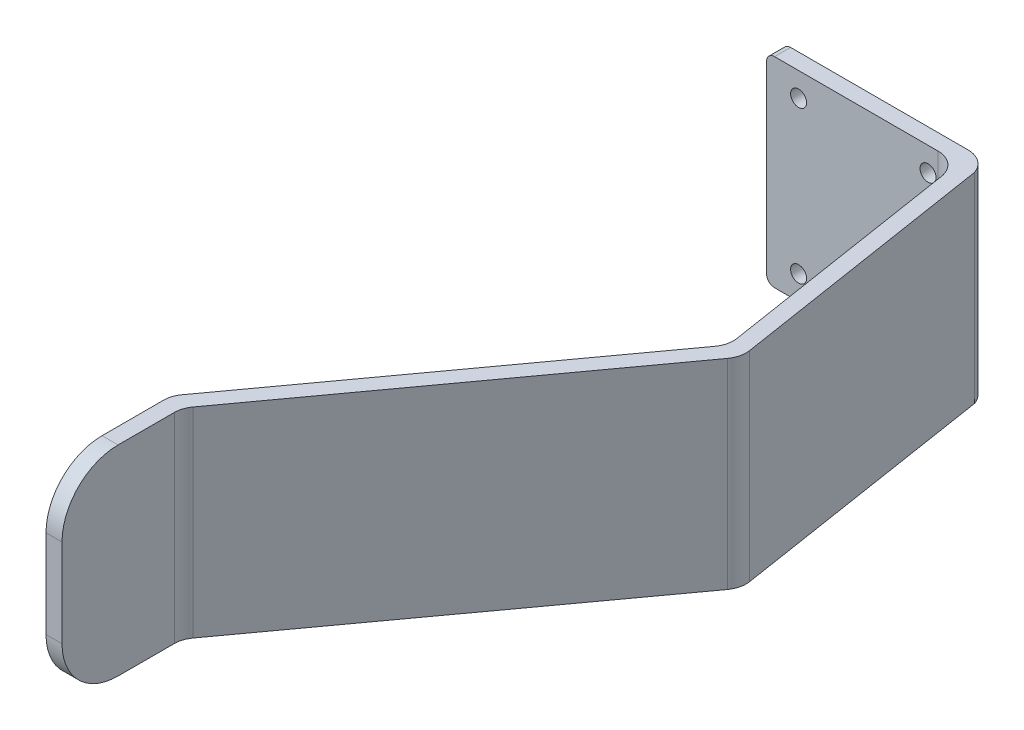
SolidWorks part; units mm, degrees
material "1060 Alloy"
ref_plane "Front Plane" through (0, 0, 0) normal (0, 0, 1) x (1, 0, 0)
ref_plane "Top Plane" through (0, 0, 0) normal (0, 1, 0) x (1, 0, 0)
ref_plane "Right Plane" through (0, 0, 0) normal (1, 0, 0) x (0, 0, -1)
sketch "Sketch1" plane through (0, 0, 0) normal (0, 1, 0) x (1, 0, 0)
  line L0 (-13, -75.3491) -> (-13, -76)
  line L1 (-13, 1) -> (13, 1)
  line L2 (-13, 1) -> (-13, -1)
  line L3 (-13, -1) -> (13, -1)
  line L4 (13, 1) -> (13, -1)
  line L5 (-13, 1) -> (13, -1) construction
  line L6 (-13, -1) -> (13, 1) construction
  line L7 (13, -1) -> (18.4271, -35.5767)
  line L8 (-13, -76) -> (-11, -76)
  line L9 (-13, -76) -> (-13, -91)
  line L10 (-13, -91) -> (-11, -91)
  line L11 (-11, -76) -> (-11, -91)
  line L12 (-11, -76) -> (18.4271, -35.5767)
  line L13 (11.0242, -1.3101) -> (16.3229, -35.0689)
  line L14 (-12.6169, -74.8229) -> (16.3229, -35.0689)
  line L15 (11.0242, -1.3101) -> (10.9755, -1)
  line L16 (-12.6169, -74.8229) -> (16.8102, -34.3996) construction
  line L17 (11.0242, -1.3101) -> (16.4513, -35.8868) construction
  line L18 (-12.6169, -74.8229) -> (-13, -75.3491)
  point P0 (0, 0)
  dimension "D1" = 26
  dimension "D2" = 2
  dimension "D4" = 15
  dimension "D5" = 2
  dimension "D6" = 35
  dimension "D7" = 50
  dimension "D8" = 2
  dimension "D9" = 2
extrude "Boss-Extrude1" add sketch "Sketch1" along normal blind 25 contours L14 L18 L0 L8 L12 L7 L3 L15 L13 | L11 L8 L9 L10 | L4 L1 L2 L3 region at (-12.151, 0, 75.5646) region at (-12, 0, 83.5) region at (0, 0, 0)
sketch "Sketch2" plane through (10.5584, 0, -1.6572) normal (-0.9879, 0, 0.1551) x (0.1551, 0, 0.9879)
  line L0 (19.9328, 12.5) -> (19.9328, 25)
  line L3 (37.1758, 25) -> (2.6898, 25) construction
  line L4 (2.6898, 25) -> (2.6898, 0) construction
  line L6 (2.6898, 12.5) -> (19.9328, 12.5)
  line L7 (19.9328, 12.5) -> (37.1758, 12.5)
  line L8 (37.1758, 25) -> (37.1758, 0) construction
  line L9 (19.9328, 12.5) -> (19.9328, 0)
  line L10 (37.1758, 0) -> (2.6898, 0) construction
  line L11 (11.3113, 12.5) -> (11.3113, 18.75)
  line L12 (11.3113, 18.75) -> (19.9328, 18.75)
  circle A0 centre (11.3113, 18.75) radius 2.5
  circle A1 centre (28.5543, 18.75) radius 2.5
  circle A2 centre (11.3113, 6.25) radius 2.5
  circle A3 centre (28.5543, 6.25) radius 2.5
  dimension "D1" = 5
extrude "Boss-Extrude2" add sketch "Sketch2" along normal blind 2 contours A1 | L11 A0 L12 | L12 A0 L11 | A2 | A3 region at (12.4769, 17.689, 10.5654) region at (12.2575, 19.1037, 9.1678) region at (14.9861, 18.75, 26.5517) region at (12.3124, 6.25, 9.5172) region at (14.9861, 6.25, 26.5517)
sketch "Sketch3" plane through (27.3553, 0, 19.914) normal (-0.8085, 0, -0.5885) x (-0.5885, 0, 0.8085)
  line L0 (18.7453, 12.5) -> (43.6568, 12.5)
  line L3 (43.6568, 0) -> (43.6568, 12.5)
  line L4 (68.5683, 0) -> (18.7453, 0) construction
  line L5 (18.7453, 25) -> (18.7453, 0) construction
  line L6 (43.6568, 12.5) -> (43.6568, 25)
  line L7 (68.5683, 25) -> (18.7453, 25) construction
  line L8 (31.2011, 12.5) -> (31.2011, 18.75)
  line L9 (31.2011, 18.75) -> (43.6568, 18.75)
  circle A0 centre (31.2011, 18.75) radius 2.5
  circle A1 centre (56.1125, 18.75) radius 2.5
  circle A2 centre (31.2011, 6.25) radius 2.5
  circle A3 centre (56.1125, 6.25) radius 2.5
  dimension "D1" = 5
extrude "Boss-Extrude3" add sketch "Sketch3" along normal blind 2 contours L8 A0 L9 | L9 A0 L8 | A2 | A3 | A1 region at (9.2003, 19.1037, 44.853) region at (8.3677, 17.689, 45.9968) region at (-5.6693, 18.75, 65.2791) region at (8.9922, 6.25, 45.139) region at (-5.6693, 6.25, 65.2791)
fillet "Fillet1" radius 2.5 8 edges at (-8.7576, 18.75, 66.1232) (-8.7576, 6.25, 66.1232) (5.9039, 6.25, 45.983) (5.9039, 18.75, 45.983) (13.3979, 18.75, 29.3316) (13.3979, 6.25, 29.3316) (10.7242, 6.25, 12.2971) (10.7242, 18.75, 12.2971)
fillet "Fillet2" radius 7 2 edges at (-12, 0, 91) (-12, 25, 91)
fillet "Fillet3" radius 1 2 edges at (-13, 0, 0) (-13, 25, 0)
fillet "Fillet4" radius 3 2 edges at (13, 12.5, -1) (10.9755, 12.5, 1)
fillet "Fillet5" radius 3 2 edges at (18.4271, 12.5, 35.5767) (16.3229, 12.5, 35.0689)
fillet "Fillet6" radius 3 2 edges at (-11, 12.5, 76) (-13, 12.5, 75.3491)
sketch "Sketch8" plane through (0, 0, -1) normal (0, 0, -1) x (-1, 0, 0)
  line L0 (-10.1716, 22) -> (-7.1716, 22)
  line L1 (-10.1716, 25) -> (-10.1716, 0) construction
  line L2 (-7.1716, 22) -> (-7.1716, 25)
  line L3 (12, 25) -> (-10.1716, 25) construction
  line L4 (-10.1716, 12.5) -> (13, 12.5)
  line L5 (13, 24) -> (13, 1) construction
  line L6 (0.9142, 25) -> (0.9142, 0)
  line L7 (12, 0) -> (-10.1716, 0) construction
  circle A0 centre (-7.1716, 22) radius 1
  circle A1 centre (-7.1716, 3) radius 1
  circle A2 centre (9, 3) radius 1
  circle A3 centre (9, 22) radius 1
  dimension "D3" = 2
  dimension "D1" = 3
  dimension "D2" = 3
extrude "Cut-Extrude2" cut sketch "Sketch8" against normal up to next contours A1 | L0 A0 L2 | L2 A0 L0 | A3 | A2 region at (7.596, 22.4244, -1) region at (7.0301, 21.8585, -1) region at (7.1716, 3, -1) region at (-9, 3, -1) region at (-9, 22, -1)
